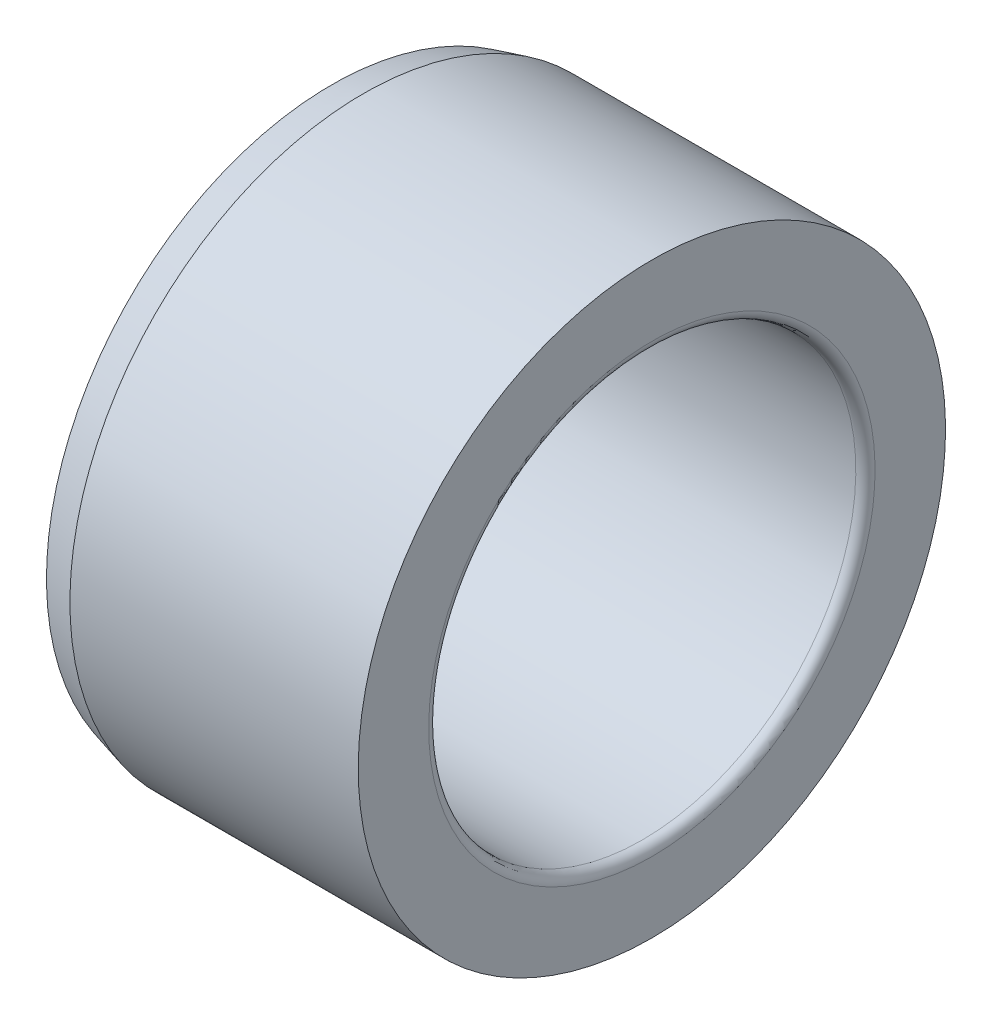
SolidWorks part; units mm, degrees
ref_plane "Front" through (0, 0, 0) normal (0, 0, 1) x (1, 0, 0)
ref_plane "Top" through (0, 0, 0) normal (0, 1, 0) x (1, 0, 0)
ref_plane "Right" through (0, 0, 0) normal (1, 0, 0) x (0, 0, -1)
sketch "Sketch1" plane through (0, 0, 0) normal (0, 0, 1) x (1, 0, 0)
  line L0 (-9.525, 0) -> (9.525, 0) construction
  line L1 (-9.525, 16.9521) -> (-7.62, 17.4625)
  line L2 (-7.62, 17.4625) -> (9.525, 17.4625)
  line L3 (-9.525, 16.9521) -> (-9.525, 12.7)
  line L4 (-9.525, 12.7) -> (8.9535, 12.7)
  line L5 (9.525, 17.4625) -> (9.525, 13.2715)
  arc A0 (8.9535, 12.7) -> (9.525, 13.2715) centre (8.9535, 13.2715) ccw
  point P2 (0, 0)
  point P11 (9.525, 12.7)
  dimension "D3" = 0.5715
  dimension "D1" = 15
  dimension "D2" = 1.905
revolve "Revolve1" add sketch "Sketch1" angle 360 about L0
ref_axis "Center Axis 1" through (8.9535, 0, 0) along (-1, 0, 0)
ref_plane "Contact Plane 1" through (-9.525, 0, 0) normal (-1, 0, 0) x (0, 0, 1)
ref_plane "Contact Plane 2" through (9.525, 0, 0) normal (1, 0, 0) x (0, 0, -1)
equation "\"D2@Sketch1\"=\"Length@Sketch1\"*.1"
equation "\"D3@Sketch1\"=\"Length@Sketch1\"*.03"
